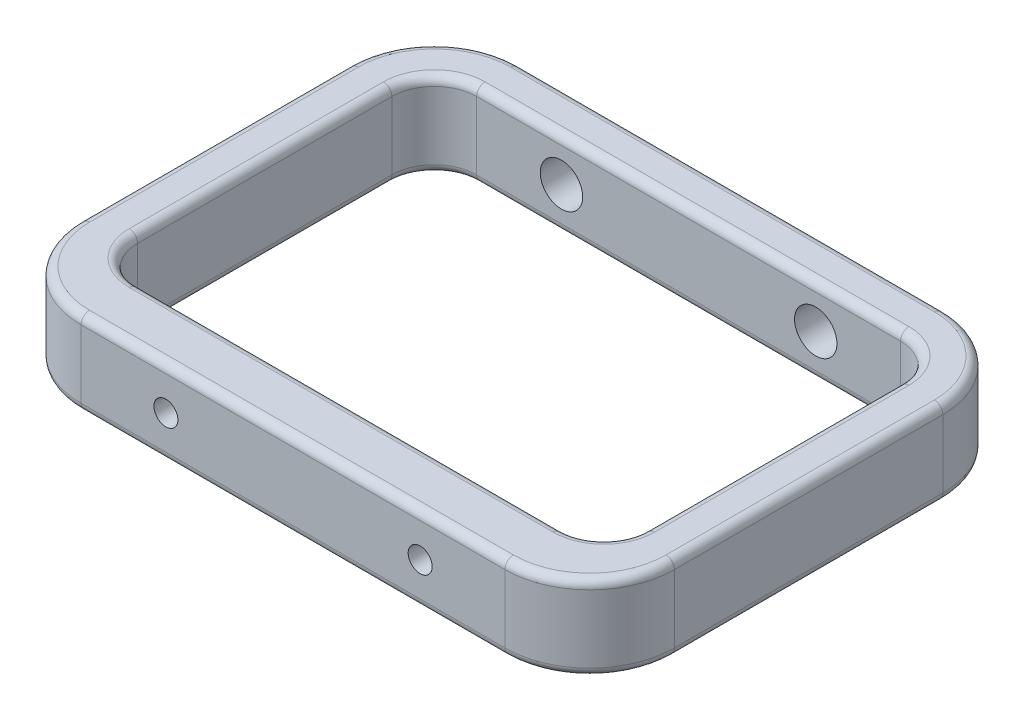
SolidWorks part; units mm, degrees
ref_plane "Front Plane" through (0, 0, 0) normal (0, 0, 1) x (1, 0, 0)
ref_plane "Top Plane" through (0, 0, 0) normal (0, 1, 0) x (1, 0, 0)
ref_plane "Right Plane" through (0, 0, 0) normal (1, 0, 0) x (0, 0, -1)
sketch "Sketch1" plane through (0, 0, 0) normal (0, 1, 0) x (1, 0, 0)
  line L0 (0, 0) -> (0, 140) construction
  line L1 (-75, 0) -> (75, 0)
  line L2 (-105, 30) -> (-105, 125)
  line L3 (-75, 140) -> (75, 140)
  line L4 (105, 30) -> (105, 125)
  line L6 (-75, 20) -> (75, 20)
  line L7 (-90, 35) -> (-90, 125)
  line L8 (-75, 155) -> (75, 155)
  line L9 (90, 35) -> (90, 125)
  arc A6 (-90, 125) -> (-75, 140) centre (-75, 125) cw
  arc A7 (75, 140) -> (90, 125) centre (75, 125) cw
  arc A8 (90, 35) -> (75, 20) centre (75, 35) cw
  arc A9 (-90, 35) -> (-75, 20) centre (-75, 35) ccw
  arc A10 (75, 155) -> (105, 125) centre (75, 125) cw
  arc A11 (-75, 155) -> (-105, 125) centre (-75, 125) ccw
  arc A12 (75, 0) -> (105, 30) centre (75, 30) ccw
  arc A13 (-75, 0) -> (-105, 30) centre (-75, 30) cw
  point P34 (-90, 140)
  point P37 (90, 140)
  point P40 (90, 20)
  dimension "D3" = 120
  dimension "D4" = 15
  dimension "D6" = 30
  dimension "D8" = 30
  dimension "D1" = 180
  dimension "D2" = 20
  dimension "D5" = 15
  dimension "D7" = 15
extrude "Boss-Extrude1" add sketch "Sketch1" along normal blind 15 and the other way blind 15
sketch "Sketch2" plane through (0, 0, 0) normal (0, 0, 1) x (1, 0, 0)
  circle A0 centre (45, 0) radius 4.25
  circle A1 centre (-45, 0) radius 4.25
  dimension "D1" = 8.5
  dimension "D2" = 8.5
  dimension "D3" = 45
  dimension "D4" = 45
extrude "Cut-Extrude1" cut sketch "Sketch2" against normal blind 120
sketch "Sketch3" plane through (0, 0, -155) normal (0, 0, -1) x (-1, 0, 0)
  circle A0 centre (45, 0) radius 7.5
  circle A1 centre (-45, 0) radius 7.5
  dimension "D1" = 15
  dimension "D2" = 15
extrude "Cut-Extrude2" cut sketch "Sketch3" against normal blind 142
fillet "Fillet1" radius 3 32 edges at (-85.6066, -15, -135.6066) (0, -15, -140) (85.6066, -15, -135.6066) (90, -15, -80) (85.6066, -15, -24.3934) (0, -15, -20) (-85.6066, -15, -24.3934) (-105, -15, -77.5) (-96.2132, -15, -146.2132) (0, -15, -155) (96.2132, -15, -146.2132) (105, -15, -77.5) (96.2132, -15, -8.7868) (0, -15, 0) (85.6066, 15, -24.3934) (0, 15, -20) (-85.6066, 15, -24.3934) (-90, 15, -80) (-85.6066, 15, -135.6066) (0, 15, -140) (85.6066, 15, -135.6066) (96.2132, 15, -146.2132) (105, 15, -77.5) (96.2132, 15, -8.7868) (0, 15, 0) (-96.2132, 15, -8.7868) (-105, 15, -77.5) (-96.2132, 15, -146.2132) (-90, -15, -80) (-96.2132, -15, -8.7868) (90, 15, -80) (0, 15, -155)
